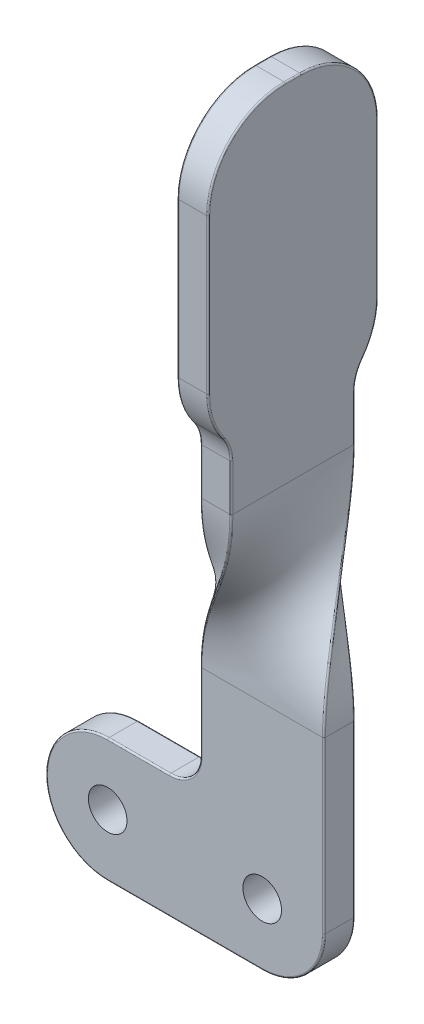
SolidWorks part; units mm, degrees
material "Plain Carbon Steel"
ref_plane "Front Plane" through (0, 0, 0) normal (0, 0, 1) x (1, 0, 0)
ref_plane "Top Plane" through (0, 0, 0) normal (0, 1, 0) x (1, 0, 0)
ref_plane "Right Plane" through (0, 0, 0) normal (1, 0, 0) x (0, 0, -1)
sketch "Sketch1" plane through (0, 0, 0) normal (0, 0, 1) x (1, 0, 0)
  line L0 (-20, 0) -> (0, 0) construction
  line L1 (-20, 8) -> (-12, 8)
  line L2 (-20, -8) -> (0, -8)
  line L3 (8, 0) -> (8, 22)
  line L4 (8, 22) -> (-8, 22)
  line L5 (-8, 22) -> (-8, 12)
  circle A0 centre (0, 0) radius 2.5
  circle A1 centre (-20, 0) radius 2.5
  arc A2 (-20, 8) -> (-20, -8) centre (-20, 0) ccw
  arc A3 (0, -8) -> (8, 0) centre (0, 0) ccw
  arc A4 (-8, 12) -> (-12, 8) centre (-12, 12) cw
  point P5 (-10, 0)
  dimension "D1" = 5
  dimension "D3" = 8
  dimension "D8" = 4
  dimension "D2" = 20
  dimension "D4" = 16
  dimension "D5" = 30
  dimension "D6" = 8
  dimension "D7" = 16
extrude "Boss-Extrude1" add sketch "Sketch1" along normal mid plane 4
ref_plane "Plane1" through (0, 38, 0) normal (0, 1, 0) x (1, 0, 0)
sketch "Sketch2" plane through (0, 38, 0) normal (0, 1, 0) x (1, 0, 0)
  line L1 (-2, -7.5) -> (2, -7.5)
  line L2 (-2, -7.5) -> (-2, 7.5)
  line L3 (-2, 7.5) -> (2, 7.5)
  line L4 (2, -7.5) -> (2, 7.5)
  line L5 (-2, -7.5) -> (2, 7.5) construction
  line L6 (-2, 7.5) -> (2, -7.5) construction
  point P0 (0, 0)
  dimension "D1" = 15
  dimension "D2" = 4
sketch "Sketch3" plane through (0, 0, 0) normal (1, 0, 0) x (0, 0, -1)
  line L0 (0, 38) -> (0, 97.757) construction
  line L1 (8, 47) -> (-8, 47)
  line L4 (-8, 47) -> (-8, 53)
  line L5 (8, 47) -> (8, 53)
  line L6 (-11, 62) -> (-11, 82)
  line L7 (11, 62) -> (11, 82)
  line L8 (-1, 92) -> (1, 92)
  line L9 (-2, 22) -> (2, 22) construction
  arc A0 (-8, 53) -> (-9, 56) centre (-13, 53) ccw
  arc A1 (8, 53) -> (9, 56) centre (13, 53) cw
  arc A2 (-9, 56) -> (-11, 62) centre (-1, 62) cw
  arc A3 (9, 56) -> (11, 62) centre (1, 62) ccw
  arc A4 (-11, 82) -> (-1, 92) centre (-1, 82) cw
  arc A5 (11, 82) -> (1, 92) centre (1, 82) ccw
  point P24 (0, 90.9251)
  dimension "D1" = 10
  dimension "D5" = 5
  dimension "D2" = 22
  dimension "D3" = 45
  dimension "D4" = 20
  dimension "D6" = 16
  dimension "D7" = 25
extrude "Boss-Extrude2" add sketch "Sketch3" along normal mid plane 4 separate body
loft "Loft1" add section face at (0, 47, 0) section face at (0, 22, 0) start constraint normal to profile start tangent length 1 end constraint normal to profile end tangent length 1 connector at (2, 47, 8) connector at (-8, 22, 2)
sketch "Sketch4" plane through (2, 0, 0) normal (1, 0, 0) x (0, 0, -1)
  line L0 (1, 92) -> (-1, 92) construction
  line L1 (1, 92) -> (-1, 92) construction
  circle A0 centre (-5, 62) radius 2.5
  point P4 (0, 92)
  dimension "D1" = 5
  dimension "D2" = 30
  dimension "D3" = 5
extrude "Cut-Extrude1" [suppressed] cut sketch "Sketch4" against normal up to next
pattern_linear "LPattern1" [suppressed] count 4 spacing 7.5 count 2 spacing 10 of bodies 104
fillet "Fillet1" radius 0.2 40 edges at (-2, 92, 0) (-2, 89.0711, -8.0711) (-2, 72, -11) (-2, 58.8377, -10.4868) (-2, 54.5811, -8.2566) (8, 11, -2) (5.6569, -5.6569, -2) (-10, -8, -2) (-28, 0, -2) (-16, 8, -2) (-9.1716, 9.1716, -2) (-8, 17, -2) (-2, 54.5811, 8.2566) (-2, 58.8377, 10.4868) (-2, 72, 11) (2, 92, 0) (2, 89.0711, -8.0711) (2, 72, -11) (2, 58.8377, -10.4868) (2, 54.5811, -8.2566) (8, 11, 2) (5.6569, -5.6569, 2) (-10, -8, 2) (-28, 0, 2) (-16, 8, 2) (-9.1716, 9.1716, 2) (-8, 17, 2) (2, 54.5811, 8.2566) (2, 58.8377, 10.4868) (2, 72, 11) (-2, 89.0711, 8.0711) (2, 89.0711, 8.0711)
